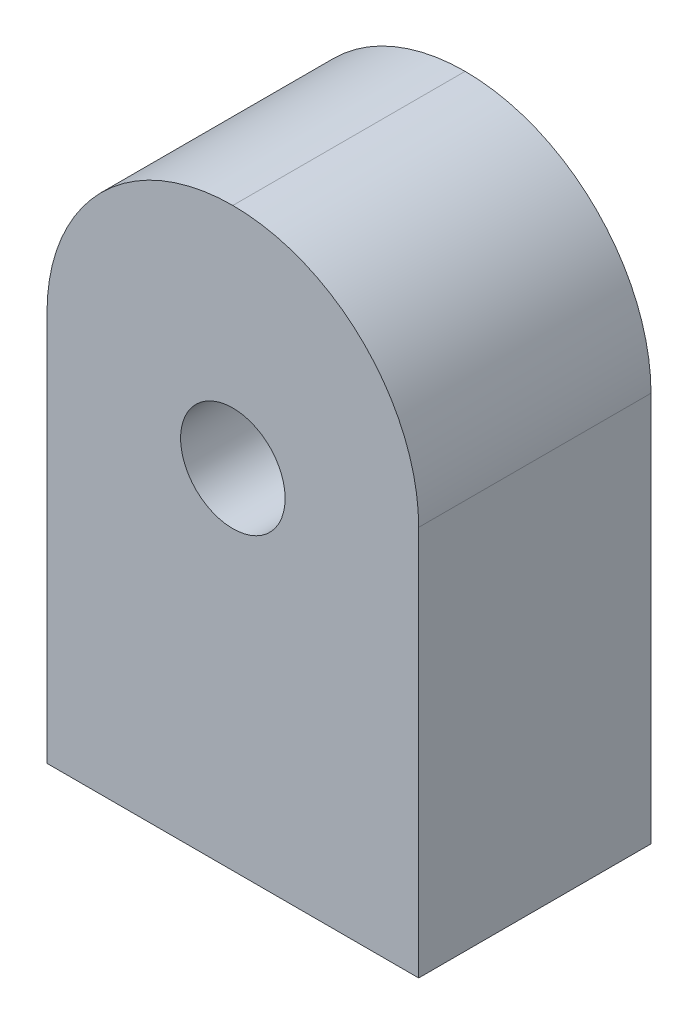
SolidWorks part; units mm, degrees
ref_plane "Front Plane" through (0, 0, 0) normal (0, 0, 1) x (1, 0, 0)
ref_plane "Top Plane" through (0, 0, 0) normal (0, 1, 0) x (1, 0, 0)
ref_plane "Right Plane" through (0, 0, 0) normal (1, 0, 0) x (0, 0, -1)
sketch "Sketch1" plane through (0, 0, 0) normal (0, 0, 1) x (1, 0, 0)
  line L1 (0, 0) -> (16, 0)
  line L2 (0, 0) -> (0, 20)
  line L3 (0, 20) -> (16, 20)
  line L4 (16, 0) -> (16, 20)
  dimension "D1" = 16
  dimension "D2" = 20
extrude "Boss-Extrude1" add sketch "Sketch1" along normal blind 10
sketch "Sketch2" plane through (0, 0, 10) normal (0, 0, 1) x (1, 0, 0)
  line L0 (8, 0) -> (8, 20) construction
  line L1 (0, 0) -> (16, 0) construction
  line L2 (16, 20) -> (0, 20) construction
  circle A0 centre (8, 10.2) radius 2.25
  dimension "D1" = 4.5
  dimension "D2" = 10.2
extrude "Cut-Extrude1" cut sketch "Sketch2" against normal through all
fillet "Fillet1" radius 8 2 edges at (16, 20, 5) (0, 20, 5)
sketch "Sketch3" plane through (0, 0, 10) normal (0, 0, 1) x (1, 0, 0)
  line L1 (0, 0) -> (16, 0)
  line L2 (0, 0) -> (0, -4.8)
  line L3 (0, -4.8) -> (16, -4.8)
  line L4 (16, 0) -> (16, -4.8)
  dimension "D1" = 4.8
extrude "Boss-Extrude2" add sketch "Sketch3" against normal blind 10
